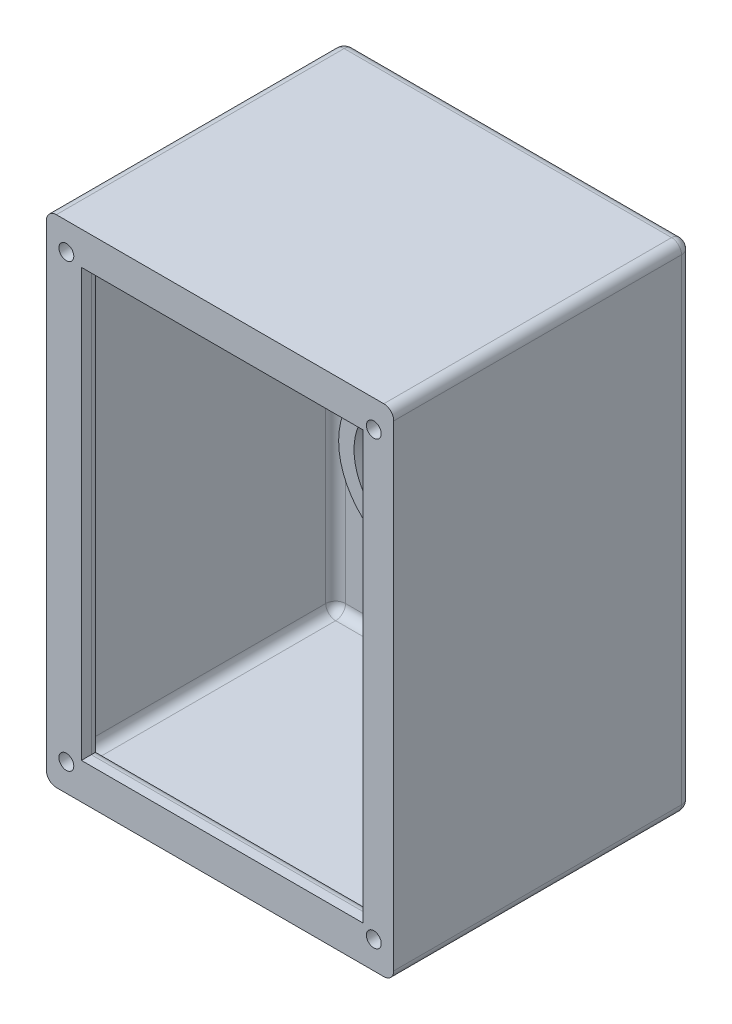
SolidWorks part; units mm, degrees
ref_plane "Plano frontal" through (0, 0, 0) normal (0, 0, 1) x (1, 0, 0)
ref_plane "Plano superior" through (0, 0, 0) normal (0, 1, 0) x (1, 0, 0)
ref_plane "Plano direito" through (0, 0, 0) normal (1, 0, 0) x (0, 0, -1)
sketch "Esboço1" plane through (0, 0, 0) normal (0, 0, 1) x (1, 0, 0)
  line L0 (-29.1211, -32.4382) -> (40.8789, -32.4382) construction
  line L1 (-29.1211, 17.5618) -> (40.8789, 17.5618)
  line L2 (-29.1211, 17.5618) -> (-29.1211, -82.4382)
  line L3 (-29.1211, -82.4382) -> (40.8789, -82.4382)
  line L4 (40.8789, 17.5618) -> (40.8789, -82.4382)
  line L5 (5.8789, 17.5618) -> (5.8789, -82.4382) construction
  circle A0 centre (5.8789, -32.4382) radius 12
  dimension "D3" = 24
  dimension "D1" = 70
  dimension "D2" = 100
extrude "Ressalto-extrusão1" add sketch "Esboço1" along normal blind 4
sketch "Esboço2" plane through (0, 0, 0) normal (0, 0, 1) x (1, 0, 0)
  circle A0 centre (5.8789, -32.4382) radius 12
  circle A1 centre (5.8789, -32.4382) radius 15.1029
extrude "Ressalto-extrusão2" add sketch "Esboço2" along normal blind 21
sketch "Esboço3" plane through (0, 0, 0) normal (0, 0, 1) x (1, 0, 0)
  line L0 (-29.1211, 17.5618) -> (40.8789, -82.4382) construction
  line L1 (-29.1211, 17.5618) -> (40.8789, 17.5618)
  line L2 (-29.1211, 17.5618) -> (-29.1211, -82.4382)
  line L3 (-29.1211, -82.4382) -> (40.8789, -82.4382)
  line L4 (40.8789, 17.5618) -> (40.8789, -82.4382)
  line L6 (-26.8272, 14.2849) -> (38.5851, 14.2849)
  line L7 (-26.8272, 14.2849) -> (-26.8272, -79.1612)
  line L8 (-26.8272, -79.1612) -> (38.5851, -79.1612)
  line L9 (38.5851, 14.2849) -> (38.5851, -79.1612)
  dimension "D1" = 4
  dimension "D2" = 4
extrude "Ressalto-extrusão3" add sketch "Esboço3" along normal blind 60
fillet "Filete1" radius 2 1 edges at (-29.1211, -32.4382, 0)
fillet "Filete2" radius 2 1 edges at (40.8789, -32.4382, 0)
fillet "Filete3" radius 2 1 edges at (-26.8272, -32.4382, 4)
fillet "Filete4" radius 2 4 edges at (-26.8272, -79.1612, 33) (-26.2414, -79.1612, 4.5858) (6.8789, -79.1612, 4) (38.5851, -32.4382, 4)
fillet "Filete5" radius 2 5 edges at (-26.8272, 14.2849, 33) (-26.2414, 14.2849, 4.5858) (38.5851, 14.2849, 33) (37.9993, 14.2849, 4.5858) (5.8789, 14.2849, 4)
sketch "Esboço4" plane through (0, 0, 0) normal (0, 0, 1) x (1, 0, 0)
  line L0 (-29.1211, 17.5618) -> (40.8789, -82.4382) construction
  line L1 (40.8789, -82.4382) -> (-29.1211, -82.4382) construction
  line L2 (-29.1211, -82.4382) -> (40.8789, 17.5618) construction
  circle A0 centre (-18.4139, 2.2659) radius 1.5
  circle A1 centre (30.1717, 2.2659) radius 1.5
  circle A2 centre (30.1717, -67.1422) radius 1.5
  circle A3 centre (-18.4139, -67.1422) radius 1.5
  dimension "D1" = 3
  dimension "D2" = 3
  dimension "D3" = 3
  dimension "D4" = 3
extrude "Corte-extrusão1" cut sketch "Esboço4" along normal blind 17 and the other way blind 14
fillet "Filete6" radius 2 5 edges at (40.8789, 17.5618, 31) (40.2931, 17.5618, 0.5858) (5.8789, 17.5618, 0) (-28.5353, 17.5618, 0.5858) (-29.1211, 17.5618, 31)
fillet "Filete7" radius 2 5 edges at (-28.5353, -82.4382, 0.5858) (5.8789, -82.4382, 0) (40.2931, -82.4382, 0.5858) (-29.1211, -82.4382, 31) (40.8789, -82.4382, 31)
sketch3d "3DSketch1"
  line L0 (-27.1211, -82.4382, 60) -> (38.8789, -82.4382, 60) construction
  line L1 (-29.1211, 15.5618, 60) -> (-29.1211, -80.4382, 60) construction
  line L2 (-26.8272, -78.6488, 60) -> (-26.8272, -81.0398, 60)
  line L3 (-26.8272, 15.9023, 60) -> (39.439, 15.9023, 60)
  line L4 (-26.8272, 15.9023, 60) -> (-26.8272, 15.5618, 60)
  line L5 (-26.8272, -81.0398, 60) -> (39.439, -81.0398, 60)
  line L6 (39.439, 15.9023, 60) -> (39.439, -81.0398, 60)
  line L7 (-22.0736, 10.9031, 60) -> (34.6571, 10.9031, 60)
  line L8 (-22.0736, 10.9031, 60) -> (-22.0736, -75.1711, 60)
  line L9 (-22.0736, -75.1711, 60) -> (34.6571, -75.1711, 60)
  line L10 (34.6571, 10.9031, 60) -> (34.6571, -75.1711, 60)
  line L11 (-29.1211, 15.5618, 60) -> (-26.8272, 15.5618, 60)
  line L12 (-29.1211, 15.5618, 60) -> (-29.1211, -78.6488, 60)
  line L13 (-29.1211, -78.6488, 60) -> (-26.8272, -78.6488, 60)
extrude "Ressalto-extrusão4" add sketch "3DSketch1" along direction (0, 0, 1) on the side against the normal blind 4
sketch "Esboço5" plane through (0, 0, 60) normal (0, 0, 1) x (1, 0, 0)
  line L0 (-28.5353, 16.9761) -> (40.2931, -81.8524) construction
  line L1 (40.2931, -81.8524) -> (40.2931, 16.9761) construction
  line L2 (40.2931, 16.9761) -> (-28.5353, -81.8524) construction
  arc A0 (-27.1211, 17.5618) -> (-29.1211, 15.5618) centre (-27.1211, 15.5618) ccw construction
  arc A1 (38.8789, -82.4382) -> (40.8789, -80.4382) centre (38.8789, -80.4382) ccw construction
  arc A2 (40.8789, 15.5618) -> (38.8789, 17.5618) centre (38.8789, 15.5618) ccw construction
  arc A3 (-29.1211, -80.4382) -> (-27.1211, -82.4382) centre (-27.1211, -80.4382) ccw construction
  circle A4 centre (-25.1063, 12.0524) radius 1.5
  circle A5 centre (36.8641, -76.9288) radius 1.5
  circle A6 centre (36.8641, 12.0524) radius 1.5
  circle A7 centre (-25.1063, -76.9288) radius 1.5
  dimension "D3" = 3
  dimension "D4" = 3
  dimension "D5" = 3
  dimension "D8" = 3
  dimension "D1" = 6
  dimension "D2" = 6
  dimension "D6" = 6
  dimension "D7" = 6
extrude "Corte-extrusão2" cut sketch "Esboço5" against normal blind 14 and the other way blind 4
fillet "Filete8" radius 2 4 edges
